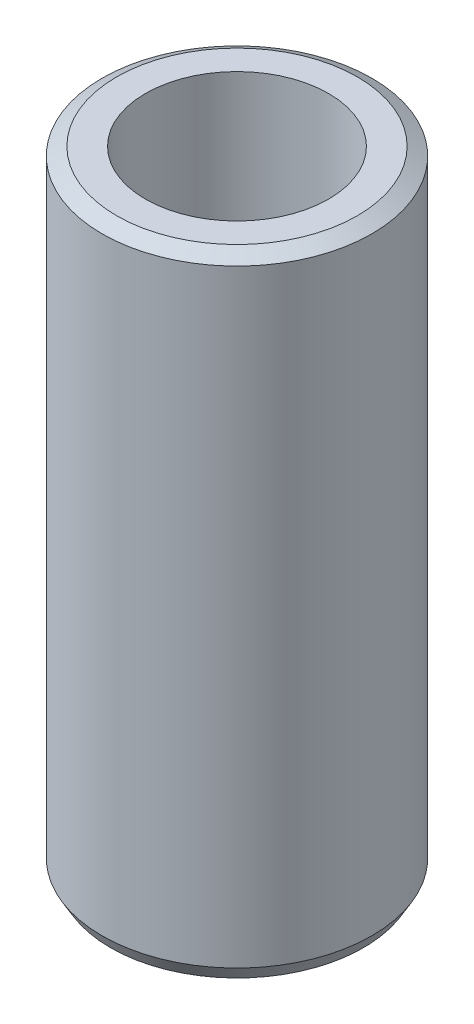
SolidWorks part; units mm, degrees
ref_plane "Front Plane" through (0, 0, 0) normal (0, 0, 1) x (1, 0, 0)
ref_plane "Top Plane" through (0, 0, 0) normal (0, 1, 0) x (1, 0, 0)
ref_plane "Right Plane" through (0, 0, 0) normal (1, 0, 0) x (0, 0, -1)
sketch "Sketch1" plane through (0, 0, 0) normal (0, 1, 0) x (1, 0, 0)
  circle A0 centre (0, 0) radius 45
  dimension "SHAFT_OD" = 90
extrude "Boss-Extrude1" add sketch "Sketch1" along normal blind 210.4963
sketch "Sketch2" plane through (0, 0, 0) normal (0, 1, 0) x (1, 0, 0)
  circle A0 centre (0, 0) radius 30.5492
  dimension "BORE_D" = 61.0984
extrude "Cut-Extrude1" cut sketch "Sketch2" along normal through all
chamfer "Chamfer1" distance 2.8022 angle 60 2 edges at (0, 210.4963, 45) (0, 0, 45) first distance on face at (0, 210.4963, 45) first distance on face at (0, 0, 30.5492)
